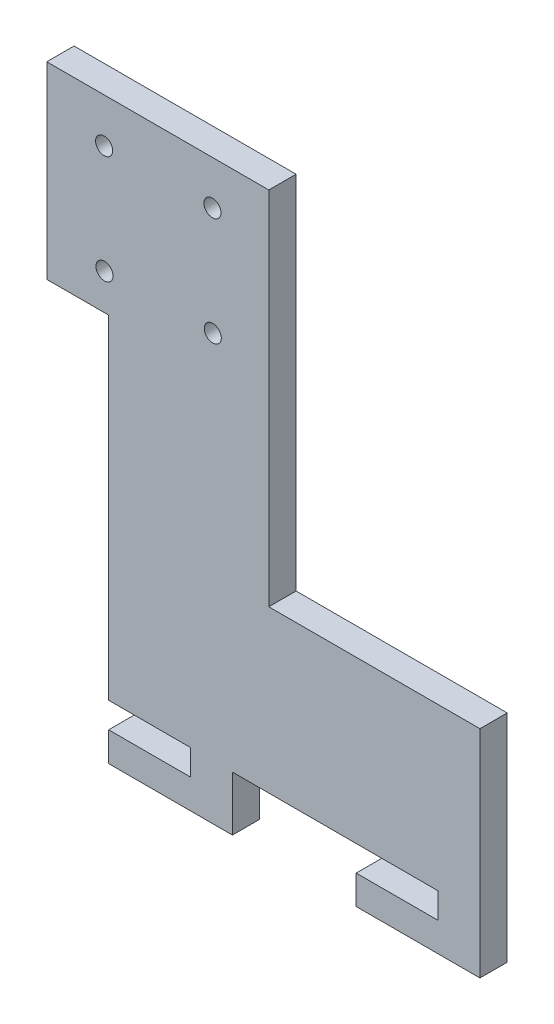
SolidWorks part; units mm, degrees
ref_plane "Front Plane" through (0, 0, 0) normal (0, 0, 1) x (1, 0, 0)
ref_plane "Top Plane" through (0, 0, 0) normal (0, 1, 0) x (1, 0, 0)
ref_plane "Right Plane" through (0, 0, 0) normal (1, 0, 0) x (0, 0, -1)
sketch "Sketch1" plane through (0, 0, 0) normal (0, 0, 1) x (1, 0, 0)
  line L1 (0, 0) -> (76.2, 0)
  line L2 (0, 0) -> (0, 96.6555)
  line L3 (0, 96.6555) -> (76.2, 96.6555)
  line L4 (76.2, 0) -> (76.2, 96.6555)
  line L5 (0, 0) -> (76.2, 96.6555) construction
  line L6 (0, 96.6555) -> (76.2, 0) construction
  point P4 (38.1, 48.3277)
  dimension "D1" = 96.6555
  dimension "D2" = 76.2
extrude "Boss-Extrude1" add sketch "Sketch1" along normal blind 4.8
sketch "Sketch4" plane through (0, 0, 4.8) normal (0, 0, 1) x (1, 0, 0)
  line L0 (76.2, 96.6555) -> (0, 96.6555) construction
  line L1 (76.2, 96.6555) -> (39.0586, 96.6555)
  line L2 (76.2, 96.6555) -> (76.2, 33.1555)
  line L3 (76.2, 33.1555) -> (39.0586, 33.1555)
  line L4 (39.0586, 96.6555) -> (39.0586, 33.1555)
  line L5 (76.2, 96.6555) -> (39.0586, 33.1555) construction
  line L6 (76.2, 33.1555) -> (39.0586, 96.6555) construction
  point P4 (57.6293, 64.9055)
  dimension "D1" = 37.1414
  dimension "D2" = 63.5
extrude "Cut-Extrude3" cut sketch "Sketch4" against normal through all
sketch "Sketch5" plane through (0, 0, 4.8) normal (0, 0, 1) x (1, 0, 0)
  line L1 (0, 0) -> (10.8857, 0)
  line L2 (0, 0) -> (0, 63.5)
  line L3 (0, 63.5) -> (10.8857, 63.5)
  line L4 (10.8857, 0) -> (10.8857, 63.5)
  line L5 (0, 0) -> (10.8857, 63.5) construction
  line L6 (0, 63.5) -> (10.8857, 0) construction
  point P5 (5.4429, 31.75)
  dimension "D1" = 63.5
  dimension "D2" = 10.8857
extrude "Cut-Extrude4" cut sketch "Sketch5" against normal through all
sketch "Sketch6" plane through (0, 0, 0) normal (0, -1, 0) x (1, 0, 0)
  line L1 (10.8857, 4.8) -> (76.2, 4.8)
  line L2 (10.8857, 4.8) -> (10.8857, 0)
  line L3 (10.8857, 0) -> (76.2, 0)
  line L4 (76.2, 4.8) -> (76.2, 0)
  line L5 (10.8857, 4.8) -> (76.2, 0) construction
  line L6 (10.8857, 0) -> (76.2, 4.8) construction
  point P4 (43.5429, 2.4)
extrude "Boss-Extrude2" add sketch "Sketch6" along normal blind 4.826
sketch "Sketch7" plane through (0, 0, 4.8) normal (0, 0, 1) x (1, 0, 0)
  line L0 (76.2, -4.826) -> (10.8857, -4.826) construction
  line L1 (32.6571, -4.826) -> (54.4286, -4.826)
  line L2 (32.6571, -4.826) -> (32.6571, 4.774)
  line L3 (32.6571, 4.774) -> (54.4286, 4.774)
  line L4 (54.4286, -4.826) -> (54.4286, 4.774)
  line L5 (32.6571, -4.826) -> (54.4286, 4.774) construction
  line L6 (32.6571, 4.774) -> (54.4286, -4.826) construction
  line L7 (10.8857, -4.826) -> (32.6571, -4.826)
  line L8 (54.4286, -4.826) -> (76.2, -4.826)
  line L10 (10.8857, -4.826) -> (10.8857, 63.5) construction
  line L11 (10.8857, 4.826) -> (25.2911, 4.826)
  line L12 (10.8857, 4.826) -> (10.8857, 0.326)
  line L13 (10.8857, 0.326) -> (25.2911, 0.326)
  line L14 (25.2911, 4.826) -> (25.2911, 0.326)
  line L15 (10.8857, 4.826) -> (25.2911, 0.326) construction
  line L16 (10.8857, 0.326) -> (25.2911, 4.826) construction
  line L17 (76.2, -4.826) -> (76.2, 33.1555) construction
  line L18 (54.4286, 4.774) -> (68.834, 4.774)
  line L19 (54.4286, 4.774) -> (54.4286, 0.274)
  line L20 (54.4286, 0.274) -> (68.834, 0.274)
  line L21 (68.834, 4.774) -> (68.834, 0.274)
  line L22 (54.4286, 4.774) -> (68.834, 0.274) construction
  line L23 (54.4286, 0.274) -> (68.834, 4.774) construction
  point P4 (43.5429, -0.026)
  point P15 (18.0884, 2.576)
  point P21 (61.6313, 2.524)
  line M3 (10.8857, 63.5) -> (10.8857, -4.826)
  line M4 (10.8857, -4.826) -> (76.2, -4.826)
  dimension "D1" = 21.7714
  dimension "D3" = 7.366
  dimension "D4" = 7.366
  dimension "D5" = 4.5
  dimension "D6" = 4.5
extrude "Cut-Extrude5" cut sketch "Sketch7" against normal through all contours L14 L11 L13 M3 | L4 L3 L2 M4 | L21 L18 L4 L20 region at (43.5429, -0.026, 4.8) region at (18.0884, 2.576, 4.8) region at (61.6313, 2.524, 4.8)
extrude "Cut-Extrude6" cut sketch "Sketch8" against normal through all
sketch "Sketch8" plane through (29.4576, -64.7284, 4.8) normal (0, 0, 1) x (1, 0, 0)
  circle A4 centre (-0.2544, 134.6311) radius 1.5
  circle A5 centre (-0.3166, 153.681) radius 1.5
  circle A6 centre (-19.3043, 134.5689) radius 1.5
  circle A7 centre (-19.3665, 153.6188) radius 1.5
equation "\"MDF\"= 4.8mm"
equation "\"Foamcore\"= 4.6mm"
equation "\"PCB\" = 1.6mm"
equation "\"GMaterial\"= \"MDF\""
equation "\"BaseWidth\" = 10in"
equation "\"SkidLength\" = 1in"
equation "\"SkidClearance\" = 0.4in"
equation "\"MotorMountLength\" = 2in"
equation "\"MotorMountWidth\" = \"GMaterial\""
equation "\"MotorMountHeight\" = 2.25in"
equation "\"UnoStackWidth\" = 77.4mm"
equation "\"UnoStackLength\" = 79.8mm"
equation "\"UnoStackHeight\" = 34.2mm"
equation "\"TallHexRiserHeight\" = 22.2mm"
equation "\"PingPongBallSize\" = 40mm"
equation "\"BarrelLength\" = 9in"
equation "\"BarrelSize\" = \"PingPongBallSize\""
equation "\"PlatformLength\" = 4in"
equation "\"PlatformWidth\" = 6in"
equation "\"WheelWidth\"= 26mm"
equation "\"WheelDiameter\"=2.99213"
equation "\"ServoMountLength\"= 1.53774"
equation "\"ServoGearHeight\" = 0.95330261in"
equation "\"PlatformMountHeight\" = 3.19"
equation "\"PivotHoleRadius\"= 0.616358"
equation "\"ServoMountReductionBackHeight\"=2.25"
equation "\"ServoMountHeight\"=2.49223"
equation "\"TensionOffSet\"= .3mm"
equation "\"MotorMountWedge\"=0.333333"
equation "\"LaserCutterOffset\"= .3mm"
equation "\"BumperWidth\"=11"
equation "\"PitcherWheelCompression\" = 2.5mm"
equation "\"PitchingWheelWidth\" = 26.2mm"
equation "\"PitchingWheelDiameter\" = 65.5mm"
equation "\"PitchingWheelMountOffset\" = 8.4mm"
equation "\"PitchingWheelInnerDiameter\" = 45.5mm"
equation "\"PitchingWheelBoltShoulder\" = 4.5mm"
equation "\"BrassCouplingLength\" = 18mm"
equation "\"PitchingMotorHeight\" = 57.0mm"
equation "\"PitchingMotorShaftTopHeight\" = \"PitchingMotorHeight\" - 44.1mm"
equation "\"PitchingMotorBodyHeight\" = 38mm"
equation "\"PitchingMotorTopShoulderHeight\" = 40.6mm - \"PitchingMotorBodyHeight\" "
equation "\"PitchingMotorBottomShoulderHeight\" = 40.2mm - \"PitchingMotorBodyHeight\""
equation "\"PitchingMotorBottomShaftHeight\" = \"PitchingMotorHeight\" - \"PitchingMotorShaftTopHeight\" - \"PitchingMotorTopShoulderHeight\" - \"PitchingMotorBodyHeight\" - \"PitchingMotorBottomShoulderHeight\""
equation "\"PitchingMotorShaftDiameter\" = 2.2mm"
equation "\"PitchingMotorBodyDiameter\" = 27.4mm"
equation "\"PitchingMotorTopShoulderDiameter\" = 9.8mm"
equation "\"PitchingMotorBottomShoulderDiameter\" = 9.8mm"
equation "\"BrassCouplingHexSize\" = 12mm"
equation "\"BrassCouplingBoreSize\" = 3.17mm"
equation "\"PitchingMotorMountingHoleDistance\" = 16mm"
equation "\"Acrylic\" = 4.4mm"
equation "\"PitchingMotorDistance\" = \"PitchingWheelDiameter\" + \"PingPongBallSize\" - \"PitcherWheelCompression\"*2"
equation "\"PitchingMotorPlatformOffset\"=1"
equation "\"ServoPlatformOffset\"=1.64173"
equation "\"BallBearingDiameter\" = 22mm"
equation "\"BallBearingWidth\" = 9mm"
equation "\"BallBearingHexShoulder\" = 9mm - 5.9mm"
equation "\"BallBearingHexSize\" = .36in"
equation "\"PlatformMountFrontReductionWidth\" =  1.46226in"
equation "\"D1@Sketch4\"=\"PlatformMountFrontReductionWidth\""
equation "\"D1@Sketch5\" = \"PlatformMountBackReductionHeight\""
equation "\"D2@Sketch5\" = \"PlatformMountBackReductionWidth\""
equation "\"PlatformMountBackReductionHeight\"= 2.5in"
equation "\"PlatformMountBackReductionWidth\"= 3/7in"
equation "\"PlatformMountFrontReductionHeight\" = 2.5in"
equation "\"D2@Sketch4\"=\"PlatformMountFrontReductionHeight\""
equation "\"PlatformBottomWidthThird\" =  0.857143in"
equation "\"D5@Sketch7\"=\"GMaterial\"-\"LaserCutterOffset\""
equation "\"D6@Sketch7\"=\"GMaterial\"-\"LaserCutterOffset\""
